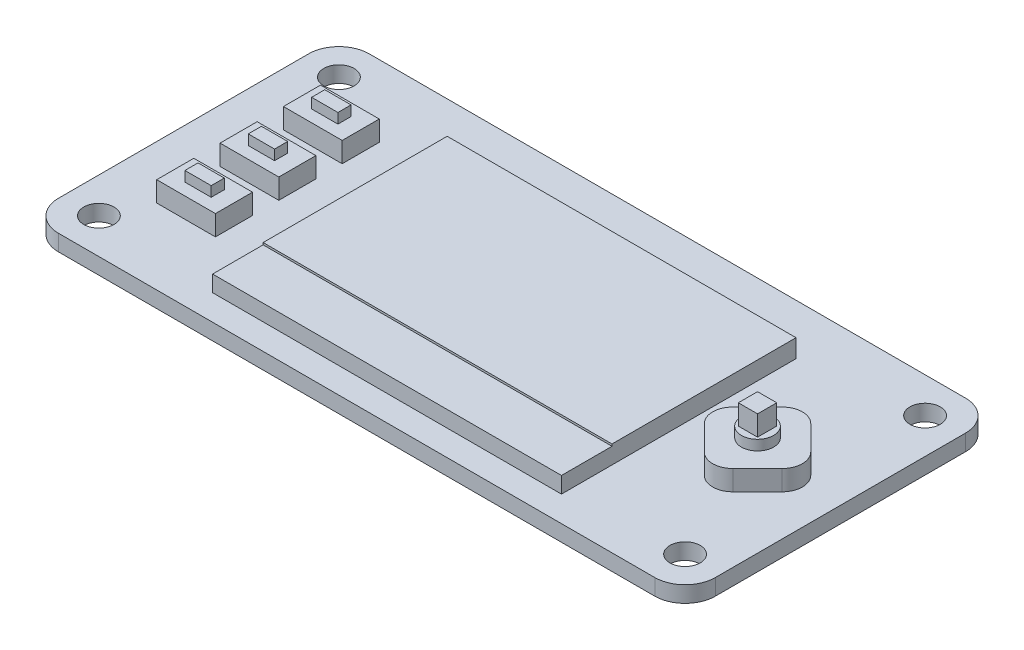
SolidWorks part; units mm, degrees
ref_plane "前视基准面" through (0, 0, 0) normal (0, 0, 1) x (1, 0, 0)
ref_plane "上视基准面" through (0, 0, 0) normal (0, 1, 0) x (1, 0, 0)
ref_plane "右视基准面" through (0, 0, 0) normal (1, 0, 0) x (0, 0, -1)
sketch "草图1" plane through (0, 0, 0) normal (0, 1, 0) x (1, 0, 0)
  line L1 (-29.5, 15.375) -> (29.5, 15.375)
  line L2 (-32.5, 12.375) -> (-32.5, -12.375)
  line L3 (-29.5, -15.375) -> (29.5, -15.375)
  line L4 (32.5, 12.375) -> (32.5, -12.375)
  line L5 (-32.5, 15.375) -> (32.5, -15.375) construction
  line L6 (-32.5, -15.375) -> (32.5, 15.375) construction
  arc A0 (-32.5, -12.375) -> (-29.5, -15.375) centre (-29.5, -12.375) ccw
  arc A1 (29.5, -15.375) -> (32.5, -12.375) centre (29.5, -12.375) ccw
  arc A2 (29.5, 15.375) -> (32.5, 12.375) centre (29.5, 12.375) cw
  arc A3 (-29.5, 15.375) -> (-32.5, 12.375) centre (-29.5, 12.375) ccw
  point P0 (0, 0)
  dimension "D3" = 3
  dimension "D1" = 30.75
  dimension "D2" = 65
extrude "凸台-拉伸1" add sketch "草图1" along normal blind 1.6
sketch "草图2" plane through (0, 1.6, 0) normal (0, 1, 0) x (1, 0, 0)
  line L0 (29.5, 15.375) -> (-29.5, 15.375) construction
  line L2 (-32.5, 12.375) -> (-32.5, -12.375) construction
  line L3 (-29.5, -15.375) -> (29.5, -15.375) construction
  line L4 (32.5, -12.375) -> (32.5, 12.375) construction
  circle A0 centre (-29, 11.875) radius 1.5
  circle A1 centre (-29, -11.875) radius 1.5
  circle A2 centre (29, -11.875) radius 1.5
  circle A3 centre (29, 11.875) radius 1.5
  dimension "D1" = 3
  dimension "D2" = 3.5
  dimension "D3" = 3.5
  dimension "D4" = 3.5
  dimension "D5" = 3.5
extrude "切除-拉伸1" cut sketch "草图2" against normal blind 1.6
sketch "草图3" plane through (0, 1.6, 0) normal (0, 1, 0) x (1, 0, 0)
  line L0 (-29.5, -15.375) -> (29.5, -15.375) construction
  line L1 (-16.78, 10.365) -> (17.74, 10.365)
  line L2 (-16.78, 10.365) -> (-16.78, -12.845)
  line L3 (-16.78, -12.845) -> (17.74, -12.845)
  line L4 (17.74, 10.365) -> (17.74, -12.845)
  line L7 (32.5, -12.375) -> (32.5, 12.375) construction
  dimension "D1" = 23.21
  dimension "D2" = 34.52
  dimension "D3" = 2.53
  dimension "D4" = 14.76
sketch "草图4" plane through (0, 1.6, 0) normal (0, 1, 0) x (1, 0, 0)
  line L0 (-29.5, -15.375) -> (29.5, -15.375) construction
  line L1 (-27.23, 8.285) -> (-21.42, 8.285)
  line L2 (-27.23, 8.285) -> (-27.23, 4.615)
  line L3 (-27.23, 4.615) -> (-21.42, 4.615)
  line L4 (-21.42, 8.285) -> (-21.42, 4.615)
  line L5 (-27.23, 2.015) -> (-21.42, 2.015)
  line L6 (-27.23, 2.015) -> (-27.23, -1.655)
  line L7 (-27.23, -1.655) -> (-21.42, -1.655)
  line L8 (-21.42, 2.015) -> (-21.42, -1.655)
  line L9 (-27.23, -4.255) -> (-21.42, -4.255)
  line L10 (-27.23, -4.255) -> (-27.23, -7.925)
  line L11 (-27.23, -7.925) -> (-21.42, -7.925)
  line L12 (-21.42, -4.255) -> (-21.42, -7.925)
  line L13 (-32.5, 12.375) -> (-32.5, -12.375) construction
  dimension "D1" = 5.81
  dimension "D2" = 3.67
  dimension "D3" = 2.6
  dimension "D4" = 2.6
  dimension "D5" = 7.45
  dimension "D6" = 5.27
sketch "草图5" plane through (0, 1.6, 0) normal (0, 1, 0) x (1, 0, 0)
  line L0 (26.0247, 3.5383) -> (28.4642, 1.0987)
  line L1 (23.1963, 3.5383) -> (20.7567, 1.0987)
  line L2 (28.4642, -1.7297) -> (26.0247, -4.1692)
  line L3 (20.7567, -1.7297) -> (23.1963, -4.1692)
  line L4 (32.5, -12.375) -> (32.5, 12.375) construction
  line L5 (-29.5, -15.375) -> (29.5, -15.375) construction
  arc A0 (26.0247, -4.1692) -> (23.1963, -4.1692) centre (24.6105, -2.755) cw
  arc A1 (20.7567, 1.0987) -> (20.7567, -1.7297) centre (22.171, -0.3155) ccw
  arc A2 (23.1963, 3.5383) -> (26.0247, 3.5383) centre (24.6105, 2.124) cw
  arc A3 (28.4642, 1.0987) -> (28.4642, -1.7297) centre (27.05, -0.3155) cw
  point P8 (19.3425, -0.3155)
  point P11 (24.6105, 4.9525)
  point P14 (29.8784, -0.3155)
  point P15 (29.05, -0.3155)
  point P18 (24.6105, -4.755)
  dimension "D3" = 2
  dimension "D1" = 7.45
  dimension "D2" = 7.45
  dimension "D4" = 3.45
  dimension "D5" = 10.62
extrude "凸台-拉伸2" add sketch "草图3" along normal blind 1.8
extrude "凸台-拉伸3" add sketch "草图5" along normal blind 2
extrude "凸台-拉伸4" add sketch "草图4" along normal blind 2
sketch "草图7" plane through (0, 3.6, 0) normal (0, 1, 0) x (1, 0, 0)
  line L0 (-21.42, 8.285) -> (-27.23, 8.285) construction
  line L1 (-25.625, 7.1) -> (-23.025, 7.1)
  line L2 (-25.625, 7.1) -> (-25.625, 5.8)
  line L3 (-25.625, 5.8) -> (-23.025, 5.8)
  line L4 (-23.025, 7.1) -> (-23.025, 5.8)
  line L5 (-25.625, 7.1) -> (-23.025, 5.8) construction
  line L6 (-25.625, 5.8) -> (-23.025, 7.1) construction
  line L7 (-25.625, 0.83) -> (-23.025, 0.83)
  line L8 (-25.625, 0.83) -> (-25.625, -0.47)
  line L9 (-25.625, -0.47) -> (-23.025, -0.47)
  line L10 (-23.025, 0.83) -> (-23.025, -0.47)
  line L11 (-25.625, 0.83) -> (-23.025, -0.47) construction
  line L12 (-25.625, -0.47) -> (-23.025, 0.83) construction
  line L13 (-25.625, -5.44) -> (-23.025, -5.44)
  line L14 (-25.625, -5.44) -> (-25.625, -6.74)
  line L15 (-25.625, -6.74) -> (-23.025, -6.74)
  line L16 (-23.025, -5.44) -> (-23.025, -6.74)
  line L17 (-25.625, -5.44) -> (-23.025, -6.74) construction
  line L18 (-25.625, -6.74) -> (-23.025, -5.44) construction
  line L19 (-27.23, -4.255) -> (-27.23, -7.925) construction
  line L20 (-27.23, 2.015) -> (-27.23, -1.655) construction
  line L21 (-27.23, 8.285) -> (-27.23, 4.615) construction
  point P0 (-24.325, 6.45)
  point P5 (-24.325, 0.18)
  point P10 (-24.325, -6.09)
  point P18 (-24.325, 8.285)
  point P22 (-27.23, -6.09)
  point P26 (-27.23, 0.18)
  point P30 (-27.23, 6.45)
  dimension "D1" = 2.6
  dimension "D2" = 1.3
extrude "凸台-拉伸5" add sketch "草图7" along normal blind 1
sketch "草图8" plane through (0, 0, 0) normal (0, -1, 0) x (1, 0, 0)
  line L0 (29.5, -15.375) -> (-29.5, -15.375) construction
  line L1 (-25.7, -8.735) -> (25.3, -8.735)
  line L2 (-25.7, -8.735) -> (-25.7, -13.735)
  line L3 (-25.7, -13.735) -> (25.3, -13.735)
  line L4 (25.3, -8.735) -> (25.3, -13.735)
  line L5 (32.5, 12.375) -> (32.5, -12.375) construction
  dimension "D1" = 5
  dimension "D2" = 51
  dimension "D3" = 1.64
  dimension "D4" = 7.2
extrude "凸台-拉伸6" add sketch "草图8" along normal blind 3.68
sketch "草图9" plane through (0, 3.6, 0) normal (0, 1, 0) x (1, 0, 0)
  line L1 (23.6605, 0.6345) -> (25.5605, 0.6345)
  line L2 (23.6605, 0.6345) -> (23.6605, -1.2655)
  line L3 (23.6605, -1.2655) -> (25.5605, -1.2655)
  line L4 (25.5605, 0.6345) -> (25.5605, -1.2655)
  line L5 (23.6605, 0.6345) -> (25.5605, -1.2655) construction
  line L6 (23.6605, -1.2655) -> (25.5605, 0.6345) construction
  arc A0 (28.4642, -1.7297) -> (28.4642, 1.0987) centre (27.05, -0.3155) ccw construction
  arc A1 (26.0247, 3.5383) -> (23.1963, 3.5383) centre (24.6105, 2.124) ccw construction
  point P0 (24.6105, -0.3155)
  point P11 (29.05, -0.3155)
  point P16 (24.6105, 4.124)
  dimension "D1" = 1.9
extrude "凸台-拉伸7" add sketch "草图9" along normal blind 3
sketch "草图10" plane through (0, 3.6, 0) normal (0, 1, 0) x (1, 0, 0)
  line L0 (25.5605, 0.6345) -> (23.6605, 0.6345) construction
  line L2 (25.5605, -1.2655) -> (25.5605, 0.6345) construction
  circle A0 centre (24.6105, -0.3155) radius 1.6
  point P5 (24.6105, 0.6345)
  point P11 (25.5605, -0.3155)
  dimension "D1" = 3.2
extrude "凸台-拉伸8" add sketch "草图10" along normal blind 1
sketch "草图11" plane through (0, 3.4, 0) normal (0, 1, 0) x (1, 0, 0)
  line L0 (17.74, -12.845) -> (17.74, 10.365) construction
  line L1 (-16.78, -12.845) -> (17.74, -12.845)
  line L2 (-16.78, -12.845) -> (-16.78, -7.845)
  line L3 (-16.78, -7.845) -> (17.74, -7.845)
  line L4 (17.74, -12.845) -> (17.74, -7.845)
  dimension "D1" = 5
extrude "切除-拉伸2" cut sketch "草图11" against normal blind 0.2
